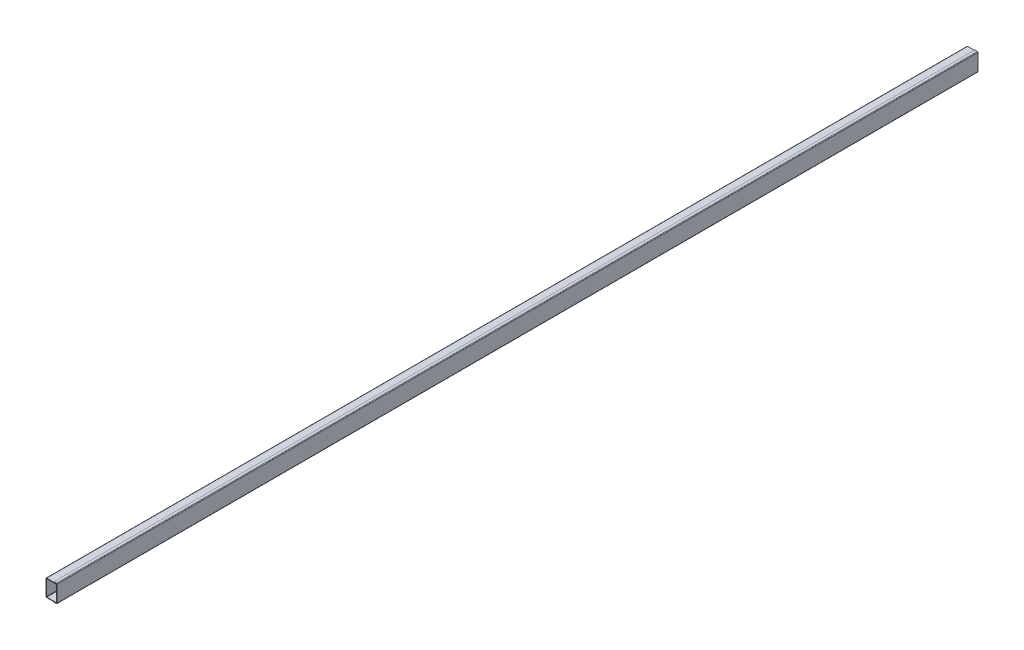
SolidWorks part; units mm, degrees
note: The reader was unsure of these and kept them because the rebuilt part matched: flange length of "Edge-Flange1", "Edge-Flange2".
ref_plane "Front Plane" through (0, 0, 0) normal (0, 0, 1) x (1, 0, 0)
ref_plane "Top Plane" through (0, 0, 0) normal (0, 1, 0) x (1, 0, 0)
ref_plane "Right Plane" through (0, 0, 0) normal (1, 0, 0) x (0, 0, -1)
sketch "Sketch1" plane through (0, 0, 0) normal (1, 0, 0) x (0, 0, -1)
  line L1 (-2185, -40) -> (2185, -40)
  line L2 (-2185, -40) -> (-2185, 40)
  line L3 (-2185, 40) -> (2185, 40)
  line L4 (2185, -40) -> (2185, 40)
  line L5 (-2185, -40) -> (2185, 40) construction
  line L6 (-2185, 40) -> (2185, -40) construction
  point P0 (0, 0)
  dimension "D1" = 4370
  dimension "D2" = 80
base flange "Base-Flange1" sketch "Sketch1" thickness 2 reverse thickness direction yes parameters "D1"=1
edge flange "Edge-Flange1" sketch "Sketch10" flange profiles "Sketch10", "Sketch11" flange angle 90 flange length 50 flange position material inside bend radius 1 thickness 2 relief rectangular parameters "D6"=10, "D8"=0.5
sketch "Sketch10" plane through (2, 40, 0) normal (0, -1, 0) x (0, 0, -1)
  line L1 (2185, 0) -> (-2185, 0) construction
  line L2 (-2185, 0) -> (-2185, 48)
  line L3 (-2185, 48) -> (2185, 48)
  line L4 (2185, 48) -> (2185, 0)
  line L5 (2185, 0) -> (-2185, 0)
sketch "Sketch11" plane through (2, -40, 0) normal (0, 1, 0) x (0, 0, 1)
  line L1 (2185, 0) -> (-2185, 0) construction
  line L2 (-2185, 0) -> (-2185, 48)
  line L3 (-2185, 48) -> (2185, 48)
  line L4 (2185, 48) -> (2185, 0)
  line L5 (2185, 0) -> (-2185, 0)
bend "EdgeBend1" bend radius 1 bend angle 90 parameters "D5"=1
bend "EdgeBend2" bend radius 1 bend angle 90 parameters "D5"=2
sketch "Sketch13" plane through (50, 0, 0) normal (1, 0, 0) x (0, 0, -1)
  line L4 (-2185, -40) -> (2185, -40)
  line L5 (2185, -40) -> (2185, 40)
  line L6 (2185, 40) -> (-2185, 40)
  line L7 (-2185, 40) -> (-2185, -40)
  line L8 (-2185, -40) -> (2185, -40)
  line L9 (2185, -40) -> (2185, 40)
  line L10 (2185, 40) -> (-2185, 40)
  line L11 (-2185, 40) -> (-2185, -40)
  dimension "D1" = 0
base flange "Base-Flange2" sketch "Sketch13" thickness 2 reverse thickness direction yes parameters "D1"=1
edge flange "Edge-Flange2" sketch "Sketch20" flange profiles "Sketch20", "Sketch21" flange angle 90 flange length 15 flange position material outside bend radius 1 thickness 2 relief rectangular parameters "D6"=10, "D8"=0.5
sketch "Sketch20" plane through (50, 40, 0) normal (0, -1, 0) x (0, 0, 1)
  line L1 (2185, 0) -> (-2185, 0) construction
  line L2 (-2185, 0) -> (-2185, 13)
  line L3 (-2185, 13) -> (2185, 13)
  line L4 (2185, 13) -> (2185, 0)
  line L5 (2185, 0) -> (-2185, 0)
sketch "Sketch21" plane through (50, -40, 0) normal (0, 1, 0) x (0, 0, -1)
  line L0 (2185, 0) -> (-2185, 0) construction
  line L1 (2185, 0) -> (-2185, 0)
  line L2 (2185, 0) -> (2185, 13)
  line L3 (2185, 13) -> (-2185, 13)
  line L4 (-2185, 13) -> (-2185, 0)
bend "EdgeBend3" bend radius 1 bend angle 90 parameters "D5"=1
bend "EdgeBend4" bend radius 1 bend angle 90 parameters "D5"=2
sketch "Bend-Lines1" [suppressed] plane through (0, 0, 0) normal (0, 1, 0) x (1, 0, 0)
sketch "Bounding-Box1" [suppressed] plane through (0, 0, 0) normal (0, 1, 0) x (1, 0, 0)
sheet metal parameters "Sheet-Metal1" thickness 2 parameters "D1"=1
flat pattern "Flat-Pattern1" [suppressed]
sketch "Bend-Lines2" plane through (0, 0, 0) normal (0, 1, 0) x (1, 0, 0)
sketch3d "Bounding-Box2" [suppressed]
  line L0 (2185, -40, 0) -> (-2185, -40, 0) construction
  line L1 (2185, 40, 0) -> (-2185, 40, 0) construction
  line L2 (2185, -40, 0) -> (2185, 40, 0) construction
  line L3 (-2185, -40, 0) -> (-2185, 40, 0) construction
sheet metal parameters "Sheet-Metal2" thickness 2 parameters "D1"=1
flat pattern "Flat-Pattern1"
sketch "Bend-Lines2" plane through (0, 0, 0) normal (-1, 0, 0) x (0, 0, 1)
  line L0 (-2185, -38.5708) -> (2185, -38.5708) construction
  line L1 (2185, 38.5708) -> (-2185, 38.5708) construction
  line L2 (-2185, -38.5708) -> (2185, -38.5708) construction
  line L3 (2185, 38.5708) -> (-2185, 38.5708) construction
sketch3d "Bounding-Box2" [suppressed]
  line L0 (-2185, -87.1416, 0) -> (2185, -87.1416, 0) construction
  line L1 (-2185, 87.1416, 0) -> (2185, 87.1416, 0) construction
  line L2 (-2185, -87.1416, 0) -> (-2185, 87.1416, 0) construction
  line L3 (2185, -87.1416, 0) -> (2185, 87.1416, 0) construction
bend of the flat pattern "Flatten-<EdgeBend1>1"
bend of the flat pattern "Flatten-<EdgeBend2>1"
sheet metal parameters "Sheet-Metal3" thickness 2 parameters "D1"=1
flat pattern "Flat-Pattern3"
sketch "Bend-Lines3" plane through (0, 0, 0) normal (0, 1, 0) x (1, 0, 0)
sketch3d "Bounding-Box3" [suppressed]
  line L0 (-2185, 40, 0) -> (2185, 40, 0) construction
  line L1 (-2185, -40, 0) -> (2185, -40, 0) construction
  line L2 (-2185, 40, 0) -> (-2185, -40, 0) construction
  line L3 (2185, 40, 0) -> (2185, -40, 0) construction
sheet metal parameters "Sheet-Metal4" thickness 2 parameters "D1"=1
flat pattern "Flat-Pattern3"
sketch "Bend-Lines3" plane through (50, 0, 0) normal (-1, 0, 0) x (0, 0, 1)
  line L0 (-2185, -40.5708) -> (2185, -40.5708) construction
  line L1 (2185, 40.5708) -> (-2185, 40.5708) construction
  line L2 (-2185, -40.5708) -> (2185, -40.5708) construction
  line L3 (2185, 40.5708) -> (-2185, 40.5708) construction
sketch3d "Bounding-Box3" [suppressed]
  line L0 (2185, 54.1416, 0) -> (-2185, 54.1416, 0) construction
  line L1 (2185, -54.1416, 0) -> (-2185, -54.1416, 0) construction
  line L2 (2185, 54.1416, 0) -> (2185, -54.1416, 0) construction
  line L3 (-2185, 54.1416, 0) -> (-2185, -54.1416, 0) construction
bend of the flat pattern "Flatten-<EdgeBend3>1"
bend of the flat pattern "Flatten-<EdgeBend4>1"
